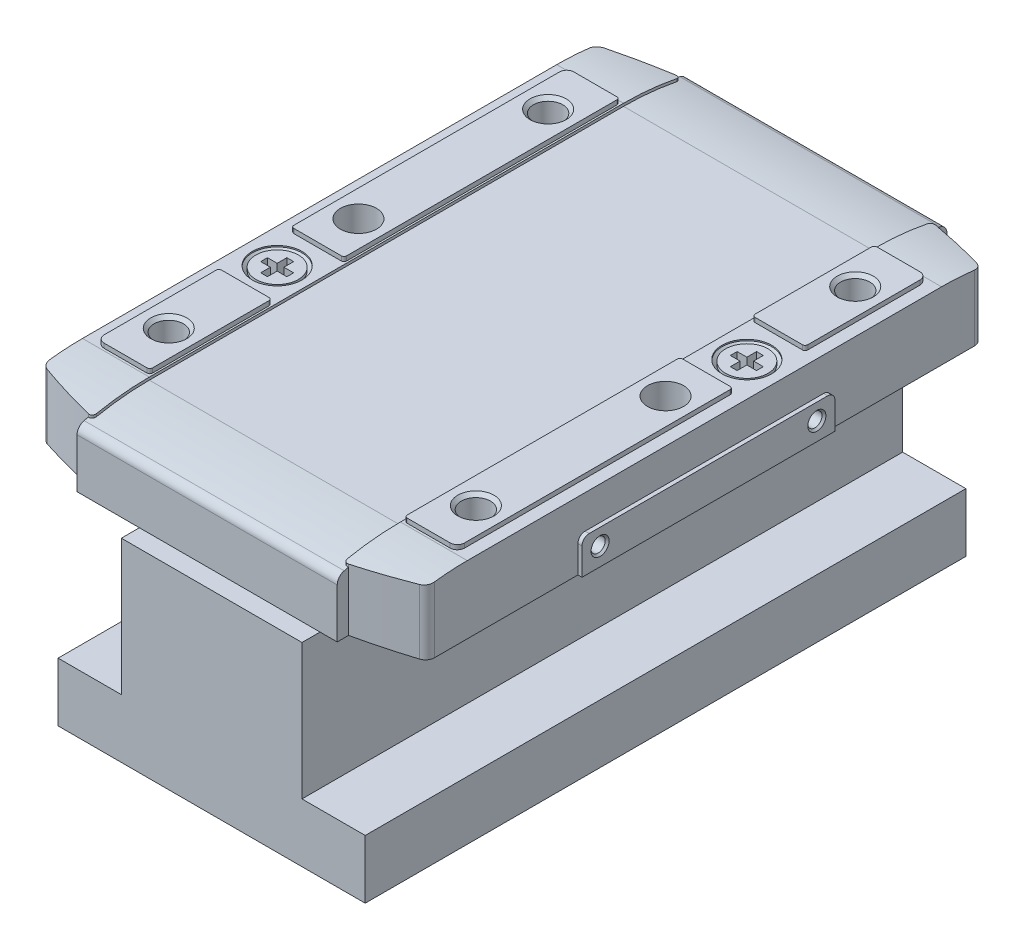
SolidWorks part; units mm, degrees
ref_plane "Front Plane" through (0, 0, 0) normal (0, 0, 1) x (1, 0, 0)
ref_plane "Top Plane" through (0, 0, 0) normal (0, 1, 0) x (1, 0, 0)
ref_plane "Right Plane" through (0, 0, 0) normal (1, 0, 0) x (0, 0, -1)
sketch "Sketch1" plane through (0, 0, 0) normal (0, 0, 1) x (1, 0, 0)
  line L0 (-17, 6.5) -> (-17, 0)
  line L1 (-17, 0) -> (17, 0)
  line L2 (17, 0) -> (17, 6.5)
  line L3 (17, 6.5) -> (10, 6.5)
  line L4 (10, 6.5) -> (10, 21.5)
  line L5 (10, 21.5) -> (-10, 21.5)
  line L6 (-10, 21.5) -> (-10, 6.5)
  line L7 (-10, 6.5) -> (-17, 6.5)
extrude "Boss-Extrude1" add sketch "Sketch1" against normal blind 33.25 and the other way blind 33.25
sketch "Sketch2" plane through (0, 0, 0) normal (0, 0, 1) x (1, 0, 0)
  line L0 (-8, 24.44) -> (-8, 21.5)
  line L1 (-8, 21.5) -> (8, 21.5)
  line L2 (8, 21.5) -> (8, 24.44)
  line L3 (8, 24.44) -> (-8, 24.44)
extrude "Boss-Extrude2" add sketch "Sketch2" against normal blind 20 and the other way blind 20
ref_plane "Plane1" through (0, 0, 28.75) normal (0, 0, 1) x (1, 0, 0)
sketch "Sketch3" plane through (0, 0, 28.75) normal (0, 0, 1) x (1, 0, 0)
  line L0 (-13.4, 22.4) -> (-8, 22.4)
  line L1 (-8, 22.4) -> (-8, 21.5)
  line L2 (-8, 21.5) -> (8, 21.5)
  line L3 (8, 21.5) -> (8, 22.4)
  line L4 (8, 22.4) -> (13.4, 22.4)
  line L5 (13.4, 22.4) -> (13.4, 22.85)
  line L6 (13.4, 22.85) -> (-13.4, 22.85)
  line L7 (-13.4, 22.85) -> (-13.4, 22.4)
extrude "Boss-Extrude3" add sketch "Sketch3" against normal blind 5
ref_plane "Plane2" through (0, 0, -28.75) normal (0, 0, 1) x (1, 0, 0)
sketch "Sketch4" plane through (0, 0, -28.75) normal (0, 0, 1) x (1, 0, 0)
  line L0 (-13.4, 22.4) -> (-8, 22.4)
  line L1 (-8, 22.4) -> (-8, 21.5)
  line L2 (-8, 21.5) -> (8, 21.5)
  line L3 (8, 21.5) -> (8, 22.4)
  line L4 (8, 22.4) -> (13.4, 22.4)
  line L5 (13.4, 22.4) -> (13.4, 22.85)
  line L6 (13.4, 22.85) -> (-13.4, 22.85)
  line L7 (-13.4, 22.85) -> (-13.4, 22.4)
extrude "Boss-Extrude4" add sketch "Sketch4" along normal blind 5
sketch "Sketch5" plane through (0, 0, 0) normal (1, 0, 0) x (0, 0, -1)
  line L0 (28.75, 22.66) -> (28.75, 24.44)
  line L1 (18.9368, 26.6155) -> (18.1845, 25.0023)
  arc A0 (18.1845, 25.0023) -> (28.75, 22.66) centre (28.75, 47.66) ccw
  arc A1 (28.75, 24.44) -> (18.9368, 26.6155) centre (28.75, 47.66) cw
extrude "Boss-Extrude5" add sketch "Sketch5" against normal blind 12.5 and the other way blind 12.5
sketch "Sketch6" plane through (0, 0, 0) normal (1, 0, 0) x (0, 0, -1)
  line L0 (-18.1845, 25.0023) -> (-18.9368, 26.6155)
  line L1 (-28.75, 24.44) -> (-28.75, 22.66)
  arc A0 (-28.75, 22.66) -> (-18.1845, 25.0023) centre (-28.75, 47.66) ccw
  arc A1 (-18.9368, 26.6155) -> (-28.75, 24.44) centre (-28.75, 47.66) cw
extrude "Boss-Extrude6" add sketch "Sketch6" against normal blind 12.5 and the other way blind 12.5
sketch "Sketch7" plane through (0, 0, 0) normal (0, 0, 1) x (1, 0, 0)
  line L0 (-13, 22.56) -> (13, 22.56)
  line L1 (13, 22.56) -> (13, 22.66)
  line L2 (13, 22.66) -> (-13, 22.66)
  line L3 (-13, 22.66) -> (-13, 22.56)
extrude "Cut-Extrude1" cut sketch "Sketch7" along normal blind 33.75 and the other way blind 33.75
sketch "Sketch8" plane through (0, 0, 0) normal (1, 0, 0) x (0, 0, -1)
  line L0 (-33.75, 29.4622) -> (-33.75, 24)
  line L1 (-33.75, 24) -> (33.75, 24)
  line L2 (33.75, 24) -> (33.75, 29.4622)
  line L3 (26.25, 31.2) -> (-26.25, 31.2)
  arc A0 (33.75, 29.4622) -> (32.9741, 30.4367) centre (32.75, 29.4622) ccw
  arc A1 (32.9741, 30.4367) -> (26.25, 31.2) centre (26.25, 1.2) ccw
  arc A2 (-26.25, 31.2) -> (-32.9741, 30.4367) centre (-26.25, 1.2) ccw
  arc A3 (-32.9741, 30.4367) -> (-33.75, 29.4622) centre (-32.75, 29.4622) ccw
extrude "Boss-Extrude7" add sketch "Sketch8" against normal blind 14.4 and the other way blind 14.4
ref_plane "Plane3" through (0, 24, 0) normal (0, 1, 0) x (1, 0, 0)
sketch "Sketch9" plane through (0, 24, 0) normal (0, 1, 0) x (1, 0, 0)
  line L0 (21.3, -29.8758) -> (21.3, 29.8758)
  line L1 (13.9, 32.1085) -> (13.9, -32.1085)
  arc A0 (13.9, -32.1085) -> (14.3852, -32.4993) centre (14.3, -32.1085) ccw
  arc A1 (14.3852, -32.4993) -> (20.6053, -30.8281) centre (0, 33.45) ccw
  arc A2 (20.6053, -30.8281) -> (21.3, -29.8758) centre (20.3, -29.8758) ccw
  arc A3 (21.3, 29.8758) -> (20.6053, 30.8281) centre (20.3, 29.8758) ccw
  arc A4 (20.6053, 30.8281) -> (14.3852, 32.4993) centre (0, -33.45) ccw
  arc A5 (14.3852, 32.4993) -> (13.9, 32.1085) centre (14.3, 32.1085) ccw
extrude "Boss-Extrude8" add sketch "Sketch9" along normal blind 7.5
sketch "Sketch10" plane through (0, 24, 0) normal (0, 1, 0) x (1, 0, 0)
  line L0 (-21.3, 29.8758) -> (-21.3, -29.8758)
  line L1 (-13.9, -32.1085) -> (-13.9, 32.1085)
  arc A0 (-21.3, -29.8758) -> (-20.6053, -30.8281) centre (-20.3, -29.8758) ccw
  arc A1 (-20.6053, -30.8281) -> (-14.3852, -32.4993) centre (0, 33.45) ccw
  arc A2 (-14.3852, -32.4993) -> (-13.9, -32.1085) centre (-14.3, -32.1085) ccw
  arc A3 (-13.9, 32.1085) -> (-14.3852, 32.4993) centre (-14.3, 32.1085) ccw
  arc A4 (-14.3852, 32.4993) -> (-20.6053, 30.8281) centre (0, -33.45) ccw
  arc A5 (-20.6053, 30.8281) -> (-21.3, 29.8758) centre (-20.3, 29.8758) ccw
extrude "Boss-Extrude9" add sketch "Sketch10" along normal blind 7.5
sketch "Sketch11" plane through (0, 0, 0) normal (1, 0, 0) x (0, 0, -1)
  line L0 (-43.75, 28) -> (-33.75, 28)
  line L1 (-33.75, 28) -> (-33.75, 30.5474)
  line L2 (-26.25, 31.5) -> (26.25, 31.5)
  line L3 (33.75, 30.5474) -> (33.75, 28)
  line L4 (33.75, 28) -> (43.75, 28)
  line L5 (43.75, 28) -> (43.75, 35)
  line L6 (43.75, 35) -> (-43.75, 35)
  line L7 (-43.75, 35) -> (-43.75, 28)
  arc A0 (-33.75, 30.5474) -> (-26.25, 31.5) centre (-26.25, 1.5) cw
  arc A1 (26.25, 31.5) -> (33.75, 30.5474) centre (26.25, 1.5) cw
extrude "Cut-Extrude2" cut sketch "Sketch11" along normal blind 30 and the other way blind 30
ref_plane "Plane4" through (0, 32, 0) normal (0, 1, 0) x (1, 0, 0)
sketch "Sketch12" plane through (0, 32, 0) normal (0, 1, 0) x (1, 0, 0)
  line L0 (14.1, 4.2) -> (14.1, -25.7)
  line L1 (14.4, -26) -> (19.15, -26)
  line L2 (19.95, -25.2) -> (19.95, 4.2)
  line L3 (19.65, 4.5) -> (14.4, 4.5)
  arc A0 (14.1, -25.7) -> (14.4, -26) centre (14.4, -25.7) ccw
  arc A1 (19.15, -26) -> (19.95, -25.2) centre (19.15, -25.2) ccw
  arc A2 (19.95, 4.2) -> (19.65, 4.5) centre (19.65, 4.2) ccw
  arc A3 (14.4, 4.5) -> (14.1, 4.2) centre (14.4, 4.2) ccw
extrude "Boss-Extrude10" add sketch "Sketch12" against normal blind 5
sketch "Sketch13" plane through (0, 32, 0) normal (0, 1, 0) x (1, 0, 0)
  line L0 (-19.65, -4.5) -> (-14.4, -4.5)
  line L1 (-14.1, -4.2) -> (-14.1, 25.7)
  line L2 (-14.4, 26) -> (-19.15, 26)
  line L3 (-19.95, 25.2) -> (-19.95, -4.2)
  arc A0 (-19.95, -4.2) -> (-19.65, -4.5) centre (-19.65, -4.2) ccw
  arc A1 (-14.4, -4.5) -> (-14.1, -4.2) centre (-14.4, -4.2) ccw
  arc A2 (-14.1, 25.7) -> (-14.4, 26) centre (-14.4, 25.7) ccw
  arc A3 (-19.15, 26) -> (-19.95, 25.2) centre (-19.15, 25.2) ccw
extrude "Boss-Extrude11" add sketch "Sketch13" against normal blind 5
sketch "Sketch14" plane through (0, 32, 0) normal (0, 1, 0) x (1, 0, 0)
  line L0 (14.1, 25.7) -> (14.1, 12.8)
  line L1 (14.4, 12.5) -> (19.65, 12.5)
  line L2 (19.95, 12.8) -> (19.95, 25.2)
  line L3 (19.15, 26) -> (14.4, 26)
  arc A0 (14.1, 12.8) -> (14.4, 12.5) centre (14.4, 12.8) ccw
  arc A1 (19.65, 12.5) -> (19.95, 12.8) centre (19.65, 12.8) ccw
  arc A2 (19.95, 25.2) -> (19.15, 26) centre (19.15, 25.2) ccw
  arc A3 (14.4, 26) -> (14.1, 25.7) centre (14.4, 25.7) ccw
extrude "Boss-Extrude12" add sketch "Sketch14" against normal blind 5
sketch "Sketch15" plane through (0, 32, 0) normal (0, 1, 0) x (1, 0, 0)
  line L0 (-19.15, -26) -> (-14.4, -26)
  line L1 (-14.1, -25.7) -> (-14.1, -12.8)
  line L2 (-14.4, -12.5) -> (-19.65, -12.5)
  line L3 (-19.95, -12.8) -> (-19.95, -25.2)
  arc A0 (-19.95, -25.2) -> (-19.15, -26) centre (-19.15, -25.2) ccw
  arc A1 (-14.4, -26) -> (-14.1, -25.7) centre (-14.4, -25.7) ccw
  arc A2 (-14.1, -12.8) -> (-14.4, -12.5) centre (-14.4, -12.8) ccw
  arc A3 (-19.65, -12.5) -> (-19.95, -12.8) centre (-19.65, -12.8) ccw
extrude "Boss-Extrude13" add sketch "Sketch15" against normal blind 5
sketch "Sketch16" plane through (0, 0, 0) normal (0, 0, 1) x (1, 0, 0)
  line L0 (17, 32) -> (19, 32)
  line L1 (19, 32) -> (19, 28.9)
  line L2 (19, 28.9) -> (17, 28.9)
  line L3 (17, 28.9) -> (17, 32)
  line L4 (17, 28.9) -> (17, 32) construction
revolve "Cut-Revolve1" cut sketch "Sketch16" angle 360 about L4 reverse direction yes
sketch "Sketch17" plane through (0, 0, 0) normal (0, 0, 1) x (1, 0, 0)
  line L0 (17, 32) -> (-17, 32)
pattern_linear "LPattern1" count 2 spacing 34 along (-1, 0, 0) of "Cut-Revolve1"
ref_plane "Plane5" through (17, 0, 0) normal (1, 0, 0) x (0, 0, -1)
sketch "Sketch18" plane through (17, 0, 0) normal (1, 0, 0) x (0, 0, -1)
  line L0 (-21, 32) -> (-19, 32)
  line L1 (-19, 32) -> (-19.379, 31.621)
  line L2 (-19.379, 31.621) -> (-19.379, 24)
  line L3 (-19.379, 24) -> (-21, 24)
  line L4 (-21, 24) -> (-21, 32)
  line L5 (-21, 24) -> (-21, 32) construction
revolve "Cut-Revolve2" cut sketch "Sketch18" angle 360 about L5 reverse direction yes
cosmetic thread "Cosmetic Thread1" parameters "D1"=8, "D2"=4
sketch "Sketch19" plane through (17, 0, 0) normal (1, 0, 0) x (0, 0, -1)
  line L0 (-21, 32) -> (21, 32)
pattern_linear "LPattern2" count 2 spacing 42 along (0, 0, -1) of "Cut-Revolve2"
cosmetic thread "Cosmetic Thread2" parameters "D1"=8, "D2"=4
ref_plane "Plane6" through (-17, 0, 0) normal (1, 0, 0) x (0, 0, -1)
sketch "Sketch20" plane through (-17, 0, 0) normal (1, 0, 0) x (0, 0, -1)
  line L0 (-21, 32) -> (-19, 32)
  line L1 (-19, 32) -> (-19.379, 31.621)
  line L2 (-19.379, 31.621) -> (-19.379, 24)
  line L3 (-19.379, 24) -> (-21, 24)
  line L4 (-21, 24) -> (-21, 32)
  line L5 (-21, 24) -> (-21, 32) construction
revolve "Cut-Revolve3" cut sketch "Sketch20" angle 360 about L5 reverse direction yes
cosmetic thread "Cosmetic Thread3" parameters "D1"=8, "D2"=4
sketch "Sketch21" plane through (-17, 0, 0) normal (1, 0, 0) x (0, 0, -1)
  line L0 (-21, 32) -> (21, 32)
pattern_linear "LPattern3" count 2 spacing 42 along (0, 0, -1) of "Cut-Revolve3"
cosmetic thread "Cosmetic Thread4" parameters "D1"=8, "D2"=4
ref_plane "Plane7" through (21.3, 0, 0) normal (1, 0, 0) x (0, 0, -1)
sketch "Sketch22" plane through (21.3, 0, 0) normal (1, 0, 0) x (0, 0, -1)
  line L0 (-14, 27) -> (-14, 24)
  line L1 (-14, 24) -> (14, 24)
  line L2 (14, 24) -> (14, 27)
  line L3 (13.2, 27.8) -> (-13.2, 27.8)
  arc A0 (14, 27) -> (13.2, 27.8) centre (13.2, 27) ccw
  arc A1 (-13.2, 27.8) -> (-14, 27) centre (-13.2, 27) ccw
extrude "Boss-Extrude14" add sketch "Sketch22" along normal blind 0.45
ref_plane "Plane8" through (-21.3, 0, 0) normal (1, 0, 0) x (0, 0, -1)
sketch "Sketch23" plane through (-21.3, 0, 0) normal (1, 0, 0) x (0, 0, -1)
  line L0 (-14, 27) -> (-14, 24)
  line L1 (-14, 24) -> (14, 24)
  line L2 (14, 24) -> (14, 27)
  line L3 (13.2, 27.8) -> (-13.2, 27.8)
  arc A0 (14, 27) -> (13.2, 27.8) centre (13.2, 27) ccw
  arc A1 (-13.2, 27.8) -> (-14, 27) centre (-13.2, 27) ccw
extrude "Boss-Extrude15" add sketch "Sketch23" against normal blind 0.45
ref_plane "Plane9" through (0, 26, 0) normal (0, 1, 0) x (1, 0, 0)
sketch "Sketch24" plane through (0, 26, 0) normal (0, 1, 0) x (1, 0, 0)
  line L0 (21.75, -12) -> (21.75, -13)
  line L1 (21.75, -13) -> (21.5335, -12.7835)
  line L2 (21.5335, -12.7835) -> (15.75, -12.7835)
  line L3 (15.75, -12.7835) -> (15.75, -12)
  line L4 (15.75, -12) -> (21.75, -12)
  line L5 (15.75, -12) -> (21.75, -12) construction
revolve "Cut-Revolve4" cut sketch "Sketch24" angle 360 about L5 reverse direction yes
cosmetic thread "Cosmetic Thread5" parameters "D1"=6, "D2"=2
sketch "Sketch25" plane through (0, 26, 0) normal (0, 1, 0) x (1, 0, 0)
  line L0 (21.75, -12) -> (21.75, 12)
pattern_linear "LPattern4" count 2 spacing 24 along (0, 0, -1) of "Cut-Revolve4"
cosmetic thread "Cosmetic Thread6" parameters "D1"=6, "D2"=2
sketch "Sketch26" plane through (0, 26, 0) normal (0, 1, 0) x (1, 0, 0)
  line L0 (-15.75, -12) -> (-15.75, -12.7835)
  line L1 (-15.75, -12.7835) -> (-21.5335, -12.7835)
  line L2 (-21.5335, -12.7835) -> (-21.75, -13)
  line L3 (-21.75, -13) -> (-21.75, -12)
  line L4 (-21.75, -12) -> (-15.75, -12)
  line L5 (-21.75, -12) -> (-15.75, -12) construction
revolve "Cut-Revolve5" cut sketch "Sketch26" angle 360 about L5 reverse direction yes
cosmetic thread "Cosmetic Thread7" parameters "D1"=6, "D2"=2
sketch "Sketch27" plane through (0, 26, 0) normal (0, 1, 0) x (1, 0, 0)
  line L0 (-21.75, -12) -> (-21.75, 12)
pattern_linear "LPattern5" count 2 spacing 24 along (0, 0, -1) of "Cut-Revolve5"
cosmetic thread "Cosmetic Thread8" parameters "D1"=6, "D2"=2
ref_plane "Plane10" through (17.5, 0, 0) normal (1, 0, 0) x (0, 0, -1)
sketch "Sketch28" plane through (17.5, 0, 0) normal (1, 0, 0) x (0, 0, -1)
  line L0 (8.5, 31.5) -> (11.25, 31.5)
  line L1 (11.25, 31.5) -> (11.25, 31.355)
  line L2 (11.25, 31.355) -> (10.85, 31)
  line L3 (10.85, 31) -> (10.85, 31.355)
  line L4 (10.85, 31.355) -> (8.5, 31.355)
  line L5 (8.5, 31.355) -> (8.5, 31.5)
  line L6 (8.5, 31.355) -> (8.5, 31.5) construction
revolve "Cut-Revolve6" cut sketch "Sketch28" angle 360 about L6 reverse direction yes
sketch "Sketch29" plane through (17.5, 0, 0) normal (1, 0, 0) x (0, 0, -1)
  line L0 (7.05, 29.8) -> (9.95, 29.8)
  line L1 (9.95, 29.8) -> (9.95, 31.5)
  line L2 (9.95, 31.5) -> (7.05, 31.5)
  line L3 (7.05, 31.5) -> (7.05, 29.8)
extrude "Cut-Extrude3" cut sketch "Sketch29" along normal blind 0.375 and the other way blind 0.375
ref_plane "Plane11" through (0, 0, -8.5) normal (0, 0, 1) x (1, 0, 0)
sketch "Sketch30" plane through (0, 0, -8.5) normal (0, 0, 1) x (1, 0, 0)
  line L0 (16.05, 29.8) -> (18.95, 29.8)
  line L1 (18.95, 29.8) -> (18.95, 31.5)
  line L2 (18.95, 31.5) -> (16.05, 31.5)
  line L3 (16.05, 31.5) -> (16.05, 29.8)
extrude "Cut-Extrude4" cut sketch "Sketch30" along normal blind 0.375 and the other way blind 0.375
ref_plane "Plane12" through (-17.5, 0, 0) normal (1, 0, 0) x (0, 0, -1)
sketch "Sketch31" plane through (-17.5, 0, 0) normal (1, 0, 0) x (0, 0, -1)
  line L0 (-8.5, 31.5) -> (-5.75, 31.5)
  line L1 (-5.75, 31.5) -> (-5.75, 31.355)
  line L2 (-5.75, 31.355) -> (-6.15, 31)
  line L3 (-6.15, 31) -> (-6.15, 31.355)
  line L4 (-6.15, 31.355) -> (-8.5, 31.355)
  line L5 (-8.5, 31.355) -> (-8.5, 31.5)
  line L6 (-8.5, 31.355) -> (-8.5, 31.5) construction
revolve "Cut-Revolve7" cut sketch "Sketch31" angle 360 about L6 reverse direction yes
sketch "Sketch32" plane through (-17.5, 0, 0) normal (1, 0, 0) x (0, 0, -1)
  line L0 (-9.95, 29.8) -> (-7.05, 29.8)
  line L1 (-7.05, 29.8) -> (-7.05, 31.5)
  line L2 (-7.05, 31.5) -> (-9.95, 31.5)
  line L3 (-9.95, 31.5) -> (-9.95, 29.8)
extrude "Cut-Extrude5" cut sketch "Sketch32" along normal blind 0.375 and the other way blind 0.375
ref_plane "Plane13" through (0, 0, 8.5) normal (0, 0, 1) x (1, 0, 0)
sketch "Sketch33" plane through (0, 0, 8.5) normal (0, 0, 1) x (1, 0, 0)
  line L0 (-18.95, 29.8) -> (-16.05, 29.8)
  line L1 (-16.05, 29.8) -> (-16.05, 31.5)
  line L2 (-16.05, 31.5) -> (-18.95, 31.5)
  line L3 (-18.95, 31.5) -> (-18.95, 29.8)
extrude "Cut-Extrude6" cut sketch "Sketch33" along normal blind 0.375 and the other way blind 0.375
ref_plane "Plane14" through (21.75, 0, 0) normal (1, 0, 0) x (0, 0, -1)
ref_plane "Plane15" through (-21.75, 0, 0) normal (1, 0, 0) x (0, 0, -1)
ref_plane "Plane16" through (0, 32, 0) normal (0, 1, 0) x (1, 0, 0)
ref_plane "ANBAU XY" through (0, 0, 0) normal (0, 0, 1) x (1, 0, 0)
ref_plane "ANBAU XZ" through (0, 0, 0) normal (0, -1, 0) x (-1, 0, 0)
ref_plane "ANBAU YZ" through (0, 0, 0) normal (1, 0, 0) x (0, 0, -1)
ref_axis "ANBAU X" through (-80.9, 0, 0) along (1, 0, 0)
ref_axis "ANBAU Y" through (0, -50, 0) along (0, 1, 0)
ref_axis "ANBAU Z" through (0, 0, 80.9) along (0, 0, -1)
sketch3d "ANBAU"
  point P0 (0, 0, 0)
ref_plane "HGOPROFIL XY" through (0, 32, 0) normal (0, -1, 0) x (-1, 0, 0)
ref_plane "HGOPROFIL XZ" through (0, 0, 0) normal (0, 0, -1) x (-1, 0, 0)
ref_plane "HGOPROFIL YZ" through (0, 0, 0) normal (1, 0, 0) x (0, 0, -1)
ref_axis "HGOPROFIL X" through (-80.9, 32, 0) along (1, 0, 0)
ref_axis "HGOPROFIL Y" through (0, 32, -50) along (0, 0, 1)
ref_axis "HGOPROFIL Z" through (0, -50, 0) along (0, 1, 0)
sketch3d "HGOPROFIL"
  point P0 (0, 32, 0)
ref_plane "SF_L XY" through (-21.75, 0, 0) normal (-1, 0, 0) x (0, 0, 1)
ref_plane "SF_L XZ" through (0, 26, 0) normal (0, 1, 0) x (1, 0, 0)
ref_plane "SF_L YZ" through (0, 0, 0) normal (0, 0, -1) x (-1, 0, 0)
ref_axis "SF_L X" through (-21.75, 26, 80.9) along (0, 0, -1)
ref_axis "SF_L Y" through (-21.75, 50, 0) along (0, -1, 0)
ref_axis "SF_L Z" through (-80.9, 26, 0) along (1, 0, 0)
sketch3d "SF_L"
  point P0 (-21.75, 26, 0)
ref_plane "SF_R XY" through (21.75, 0, 0) normal (1, 0, 0) x (0, 0, -1)
ref_plane "SF_R XZ" through (0, 26, 0) normal (0, -1, 0) x (-1, 0, 0)
ref_plane "SF_R YZ" through (0, 0, 0) normal (0, 0, -1) x (-1, 0, 0)
ref_axis "SF_R X" through (21.75, 26, 80.9) along (0, 0, -1)
ref_axis "SF_R Y" through (21.75, -50, 0) along (0, 1, 0)
ref_axis "SF_R Z" through (80.9, 26, 0) along (-1, 0, 0)
sketch3d "SF_R"
  point P0 (21.75, 26, 0)
other "Freeze***"
